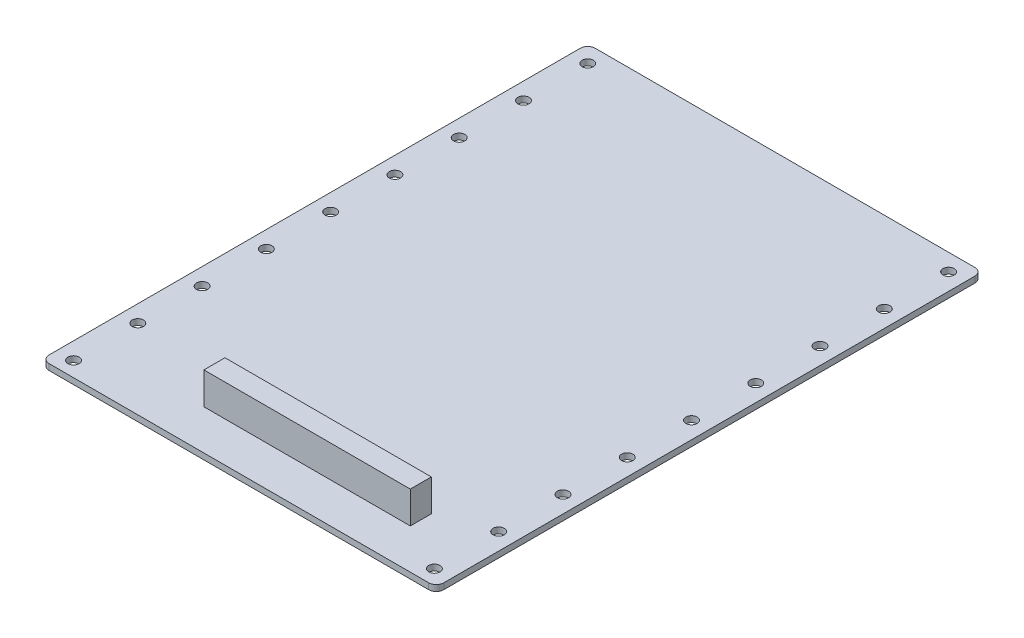
SolidWorks part; units mm, degrees
ref_plane "Front Plane" through (0, 0, 0) normal (0, 0, 1) x (1, 0, 0)
ref_plane "Top Plane" through (0, 0, 0) normal (0, 1, 0) x (1, 0, 0)
ref_plane "Right Plane" through (0, 0, 0) normal (1, 0, 0) x (0, 0, -1)
sketch "Sketch1" plane through (0, 0, 0) normal (0, 1, 0) x (1, 0, 0)
  line L1 (-52.5, -72.65) -> (52.5, -72.65)
  line L2 (-52.5, -72.65) -> (-52.5, 72.65)
  line L3 (-52.5, 72.65) -> (52.5, 72.65)
  line L4 (52.5, -72.65) -> (52.5, 72.65)
  line L5 (-52.5, -72.65) -> (52.5, 72.65) construction
  line L6 (-52.5, 72.65) -> (52.5, -72.65) construction
  point P0 (0, 0)
  dimension "D1" = 105
  dimension "D2" = 145.3
extrude "Boss-Extrude1" add sketch "Sketch1" along normal blind 1.6
sketch "Sketch3" plane through (0, 1.6, 0) normal (0, 1, 0) x (1, 0, 0)
  line L0 (0, 72.65) -> (0, -72.65) construction
  line L1 (52.5, 72.65) -> (-52.5, 72.65) construction
  line L2 (-52.5, -72.65) -> (52.5, -72.65) construction
  line L4 (-52.5, 72.65) -> (-52.5, -72.65) construction
  circle A1 centre (-48, -68.65) radius 1.5
  circle A3 centre (-48, -51.55) radius 1.5
  circle A4 centre (-48, -34.45) radius 1.5
  circle A5 centre (-48, -17.35) radius 1.5
  circle A6 centre (-48, -0.25) radius 1.5
  circle A7 centre (-48, 16.85) radius 1.5
  circle A8 centre (-48, 33.95) radius 1.5
  circle A9 centre (-48, 51.05) radius 1.5
  circle A10 centre (-48, 68.15) radius 1.5
  circle A11 centre (48, 68.15) radius 1.5
  circle A12 centre (48, 51.05) radius 1.5
  circle A13 centre (48, 33.95) radius 1.5
  circle A14 centre (48, 16.85) radius 1.5
  circle A15 centre (48, -0.25) radius 1.5
  circle A16 centre (48, -17.35) radius 1.5
  circle A17 centre (48, -34.45) radius 1.5
  circle A18 centre (48, -51.55) radius 1.5
  circle A19 centre (48, -68.65) radius 1.5
  dimension "D1" = 3
  dimension "D2" = 4.5
  dimension "D3" = 9
  dimension "D4" = 17.1
  dimension "D5" = 4
extrude "Cut-Extrude2" cut sketch "Sketch3" against normal up to surface (1.6 mm away) up to face at (0, 0, 0)
sketch "Sketch4" plane through (0, 1.6, 0) normal (0, 1, 0) x (1, 0, 0)
  line L0 (-52.5, -72.65) -> (52.5, -72.65) construction
  line L1 (-19.955, -62.0099) -> (34.955, -62.0099)
  line L2 (-19.955, -62.0099) -> (-19.955, -56.4099)
  line L3 (-19.955, -56.4099) -> (34.955, -56.4099)
  line L4 (34.955, -62.0099) -> (34.955, -56.4099)
  line L5 (-19.955, -62.0099) -> (34.955, -56.4099) construction
  line L6 (-19.955, -56.4099) -> (34.955, -62.0099) construction
  line L8 (52.5, -72.65) -> (52.5, 72.65) construction
  point P0 (7.5, -59.2099)
  dimension "D1" = 5.6
  dimension "D2" = 54.91
  dimension "D3" = 10.6401
  dimension "D4" = 45
extrude "Boss-Extrude2" add sketch "Sketch4" along normal blind 8.5
fillet "Fillet2" radius 2 4 edges at (-52.5, 0.8, -72.65) (52.5, 0.8, -72.65) (52.5, 0.8, 72.65) (-52.5, 0.8, 72.65)
